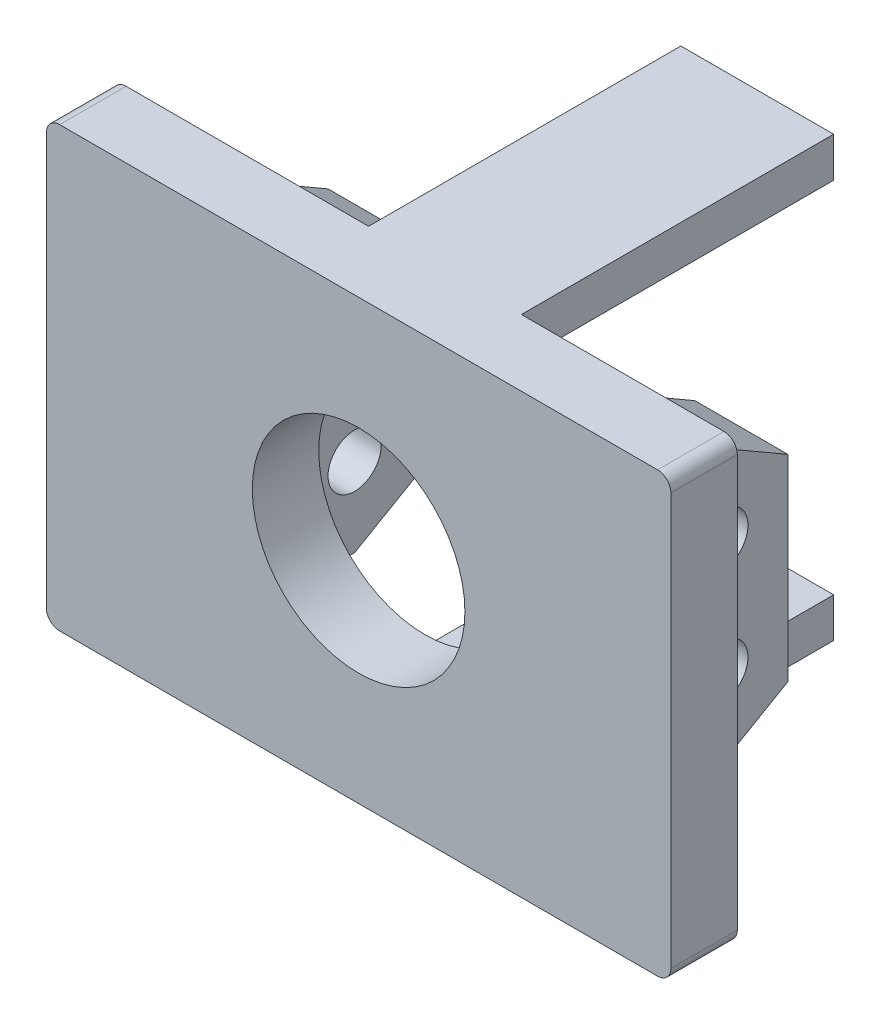
SolidWorks part; units mm, degrees
material "ABS"
ref_plane "Płaszczyzna przednia" through (0, 0, 0) normal (0, 0, 1) x (1, 0, 0)
ref_plane "Płaszczyzna górna" through (0, 0, 0) normal (0, 1, 0) x (1, 0, 0)
ref_plane "Płaszczyzna prawa" through (0, 0, 0) normal (1, 0, 0) x (0, 0, -1)
sketch "Szkic1" plane through (0, 0, 0) normal (0, 0, 1) x (1, 0, 0)
  line L1 (-23.5, -16.5) -> (23.5, -16.5)
  line L2 (-23.5, -16.5) -> (-23.5, 16.5)
  line L3 (-23.5, 16.5) -> (23.5, 16.5)
  line L4 (23.5, -16.5) -> (23.5, 16.5)
  line L5 (-23.5, -16.5) -> (23.5, 16.5) construction
  line L6 (-23.5, 16.5) -> (23.5, -16.5) construction
  circle A0 centre (0, 0) radius 8
  point P0 (0, 0)
  dimension "D3" = 16
  dimension "D1" = 33
  dimension "D2" = 47
extrude "Dodanie-wyciągnięcie1" add sketch "Szkic1" along normal blind 5
sketch "Szkic2" plane through (0, 0, 0) normal (0, 0, -1) x (-1, 0, 0)
  line L0 (23.5, -16.5) -> (-23.5, -16.5) construction
  line L1 (-17.3, -10.3) -> (-10.3, -10.3)
  line L2 (-17.3, -10.3) -> (-17.3, 10.3)
  line L3 (-17.3, 10.3) -> (-10.3, 10.3)
  line L4 (-10.3, -10.3) -> (-10.3, 10.3)
  line L5 (-17.3, -10.3) -> (-10.3, 10.3) construction
  line L6 (-17.3, 10.3) -> (-10.3, -10.3) construction
  line L7 (10.3, -10.3) -> (17.3, -10.3)
  line L8 (10.3, -10.3) -> (10.3, 10.3)
  line L9 (10.3, 10.3) -> (17.3, 10.3)
  line L10 (17.3, -10.3) -> (17.3, 10.3)
  line L11 (10.3, -10.3) -> (17.3, 10.3) construction
  line L12 (10.3, 10.3) -> (17.3, -10.3) construction
  line L14 (-23.5, 16.5) -> (23.5, 16.5) construction
  line L15 (-23.5, -16.5) -> (-23.5, 16.5) construction
  line L16 (23.5, 16.5) -> (23.5, -16.5) construction
  point P0 (-13.8, 0)
  point P5 (13.8, 0)
  dimension "D1" = 6.2
  dimension "D2" = 7
  dimension "D3" = 6.2
  dimension "D4" = 6.2
  dimension "D5" = 6.2
extrude "Dodanie-wyciągnięcie2" add sketch "Szkic2" along normal blind 10
chamfer "Sfazowanie1" distance 5 angle 30 4 edges at (13.8, 10.3, -10) (-13.8, 10.3, -10) (-13.8, -10.3, -10) (13.8, -10.3, -10) first distance on face at (13.8, 10.3, -5) first distance on face at (-13.8, 10.3, -5) first distance on face at (-13.8, -10.3, -5) first distance on face at (13.8, -10.3, -5)
sketch "Szkic3" plane through (17.3, 0, 0) normal (1, 0, 0) x (0, 0, -1)
  line L0 (0, -16.5) -> (0, 16.5) construction
  line L1 (5, -10.3) -> (0, -10.3) construction
  line L2 (5, 10.3) -> (0, 10.3) construction
  circle A0 centre (5, 4.3) radius 2
  circle A1 centre (5, -4.3) radius 2
  point P4 (0, 0)
  dimension "D1" = 4
  dimension "D2" = 5
  dimension "D3" = 6
  dimension "D4" = 6
extrude "Wytnij-wyciągnięcie1" cut sketch "Szkic3" against normal through all
fillet "Zaokrąglenie1" radius 1 4 edges at (-23.5, -16.5, 2.5) (23.5, -16.5, 2.5) (-23.5, 16.5, 2.5) (23.5, 16.5, 2.5)
sketch "Szkic4" plane through (0, 0, 0) normal (0, 0, -1) x (-1, 0, 0)
  line L0 (-22.5, 16.5) -> (22.5, 16.5) construction
  line L1 (-7.25, 16.5) -> (4.25, 16.5)
  line L2 (-7.25, 16.5) -> (-7.25, 13.5)
  line L3 (-7.25, 13.5) -> (4.25, 13.5)
  line L4 (4.25, 16.5) -> (4.25, 13.5)
  line L5 (-23.5, -15.5) -> (-23.5, 15.5) construction
  line L7 (23.5, 15.5) -> (23.5, -15.5) construction
  line L8 (22.5, -16.5) -> (-22.5, -16.5) construction
  line L9 (-7.25, -16.5) -> (4.75, -16.5)
  line L10 (-7.25, -16.5) -> (-7.25, -13.5197)
  line L11 (-7.25, -13.5197) -> (4.75, -13.5197)
  line L12 (4.75, -16.5) -> (4.75, -13.5197)
  point P16 (0, 0)
  dimension "D1" = 3
  dimension "D2" = 19.25
  dimension "D3" = 16.25
  dimension "D4" = 2.9803
  dimension "D5" = 12
extrude "Dodanie-wyciągnięcie3" add sketch "Szkic4" along normal blind 23.5
